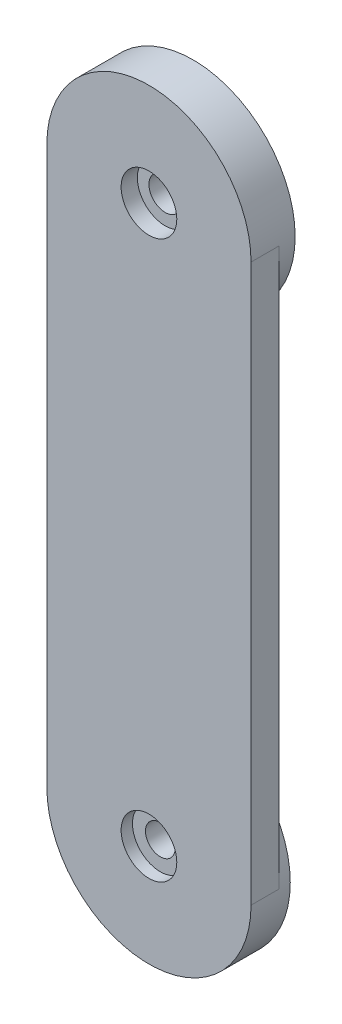
SolidWorks part; units mm, degrees
ref_plane "Front Plane" through (0, 0, 0) normal (0, 0, 1) x (1, 0, 0)
ref_plane "Top Plane" through (0, 0, 0) normal (0, 1, 0) x (1, 0, 0)
ref_plane "Right Plane" through (0, 0, 0) normal (1, 0, 0) x (0, 0, -1)
sketch "Sketch1" plane through (0, 0, 0) normal (0, 0, 1) x (1, 0, 0)
  line L0 (0, 30) -> (0, -30) construction
  line L1 (-11, 30) -> (-11, -30)
  line L2 (11, 30) -> (11, -30)
  circle A0 centre (0, 30) radius 11
  circle A1 centre (0, -30) radius 11
  point P8 (0, 0)
  dimension "D2" = 22
  dimension "D1" = 60
extrude "Boss-Extrude1" add sketch "Sketch1" along normal blind 3 contours A0 | L0 A0 L1 A1 | A1 | A0 L0 A1 L2 region at (5.8363, 0, 0) region at (-5.8363, 0, 0) region at (-7.5582, 22.4418, 0) region at (7.5582, -22.4418, 0)
extrude "Boss-Extrude2" add sketch "Sketch1<3>" against normal blind 1.75 contours A0 region at (0, 30, 0)
sketch "Sketch1<3>" plane through (0, 0, 0) normal (0, 0, 1) x (1, 0, 0) same geometry as "Sketch1"
sketch "Sketch2" plane through (0, 0, 3) normal (0, 0, 1) x (1, 0, 0)
  circle A0 centre (0, 30) radius 1.75
  circle A3 centre (0, 30) radius 3
  dimension "D1" = 3.5
  dimension "D2" = 6
extrude "Cut-Extrude1" cut sketch "Sketch2" against normal up to surface (4.75 mm away) contours A0 region at (0, 30, 3) up to face at (11, 30, -1.75)
extrude "Cut-Extrude2" cut sketch "Sketch2<3>" against normal offset from surface (1.75 mm away) 3 contours A3 A0 region at (-2.9151, 30, 3) up to face at (1.75, 30, -1.75)
sketch "Sketch2<3>" plane through (0, 0, 3) normal (0, 0, 1) x (1, 0, 0) same geometry as "Sketch2"
extrude "Boss-Extrude3" add sketch "Sketch1<4>" against normal blind 1.225 contours A1 region at (0, -30, 0)
sketch "Sketch1<4>" plane through (0, 0, 0) normal (0, 0, 1) x (1, 0, 0) same geometry as "Sketch1"
sketch "Sketch3" plane through (0, 0, 3) normal (0, 0, 1) x (1, 0, 0)
  circle A0 centre (0, -30) radius 1.6
  circle A1 centre (0, -30) radius 3
  dimension "D1" = 3.2
  dimension "D2" = 6
extrude "Cut-Extrude3" cut sketch "Sketch3" against normal up to surface (4.225 mm away) contours A0 region at (0, -30, 3) up to face at (11, -30, -1.225)
extrude "Cut-Extrude4" cut sketch "Sketch3<3>" against normal offset from surface (1.225 mm away) 3 up to face at (1.6, -30, -1.225)
sketch "Sketch3<3>" plane through (0, 0, 3) normal (0, 0, 1) x (1, 0, 0) same geometry as "Sketch3"
